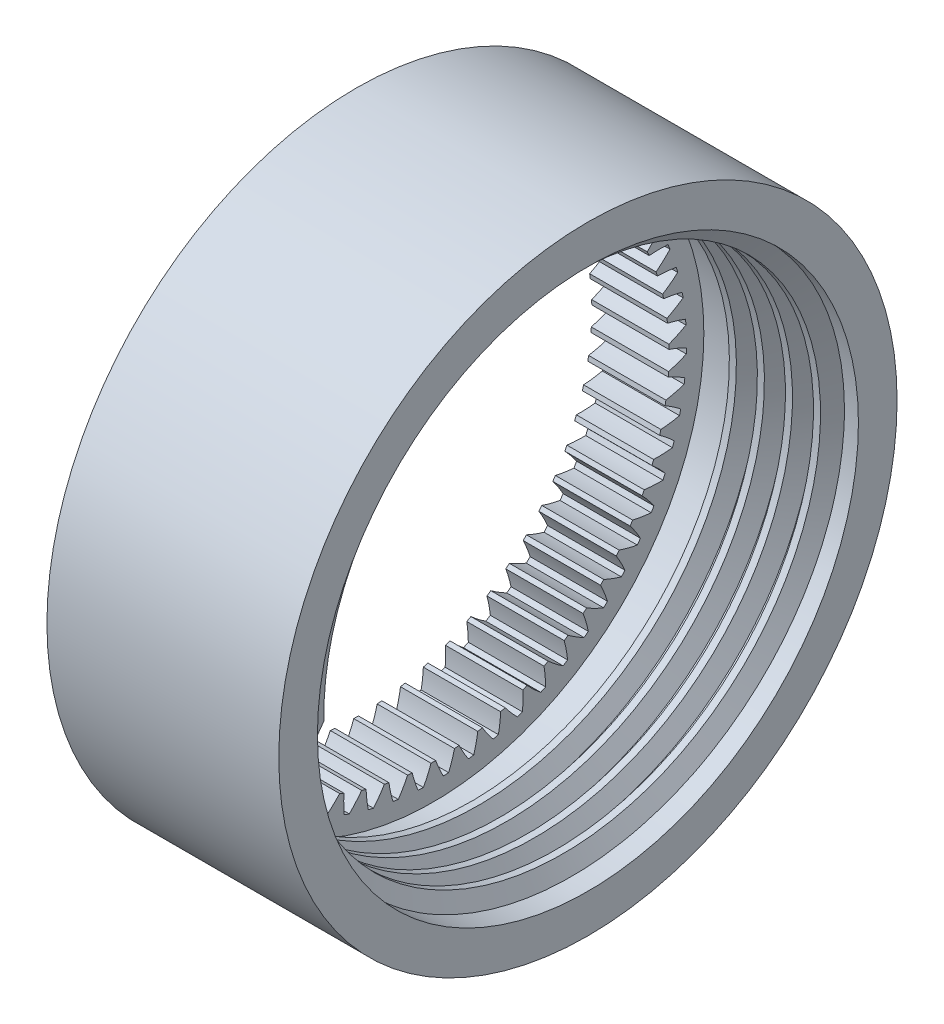
SolidWorks part; units mm, degrees
ref_plane "Front Plane" through (0, 0, 0) normal (0, 0, 1) x (1, 0, 0)
ref_plane "Top Plane" through (0, 0, 0) normal (0, 1, 0) x (1, 0, 0)
ref_plane "Right Plane" through (0, 0, 0) normal (1, 0, 0) x (0, 0, -1)
ref_plane "Plane1" through (-10.9631, 0, 0) normal (1, 0, 0) x (0, 0, -1)
sketch "Sketch1" plane through (-10.9631, 0, 0) normal (1, 0, 0) x (0, 0, -1)
  circle A0 centre (-14.8751, -9.4962) radius 40
  arc A1 (-13.054, 20.9494) -> (-11.9585, 23.1247) centre (1.5185, 14.9741) cw
  arc A2 (-11.9585, 23.1247) -> (-11.2701, 23.0558) centre (-14.8751, -9.4962) cw
  arc A3 (-11.2701, 23.0558) -> (-10.6273, 20.7066) centre (-26.0949, 17.7372) cw
  arc A4 (-10.6273, 20.7066) -> (-10.0317, 20.6168) centre (-14.8751, -9.4962) cw
  arc A5 (-10.0317, 20.6168) -> (-8.725, 22.6722) centre (3.8735, 13.2202) cw
  arc A6 (-8.725, 22.6722) -> (-8.0468, 22.5351) centre (-14.8751, -9.4962) cw
  arc A7 (-8.0468, 22.5351) -> (-7.6412, 20.1336) centre (-23.3275, 18.7191) cw
  arc A8 (-7.6412, 20.1336) -> (-7.0574, 19.9849) centre (-14.8751, -9.4962) cw
  arc A9 (-7.0574, 19.9849) -> (-5.5526, 21.9) centre (6.0421, 11.2406) cw
  arc A10 (-5.5526, 21.9) -> (-4.8915, 21.6961) centre (-14.8751, -9.4962) cw
  arc A11 (-4.8915, 21.6961) -> (-4.727, 19.2661) centre (-20.4762, 19.4204) cw
  arc A12 (-4.727, 19.2661) -> (-4.1609, 19.0601) centre (-14.8751, -9.4962) cw
  arc A13 (-4.1609, 19.0601) -> (-2.4729, 20.8158) centre (8.0029, 9.0549) cw
  arc A14 (-2.4729, 20.8158) -> (-1.8353, 20.5471) centre (-14.8751, -9.4962) cw
  arc A15 (-1.8353, 20.5471) -> (-1.9136, 18.1127) centre (-17.5692, 19.8344) cw
  arc A16 (-1.9136, 18.1127) -> (-1.3709, 17.8514) centre (-14.8751, -9.4962) cw
  arc A17 (-1.3709, 17.8514) -> (0.4835, 19.4303) centre (9.7363, 6.6848) cw
  arc A18 (0.4835, 19.4303) -> (1.0912, 19.0994) centre (-14.8751, -9.4962) cw
  arc A19 (1.0912, 19.0994) -> (0.7709, 16.685) centre (-14.6354, 19.9569) cw
  arc A20 (0.7709, 16.685) -> (1.2849, 16.3709) centre (-14.8751, -9.4962) cw
  arc A21 (1.2849, 16.3709) -> (3.2874, 17.7574) centre (11.2251, 4.1539) cw
  arc A22 (3.2874, 17.7574) -> (3.8591, 17.3676) centre (-14.8751, -9.4962) cw
  arc A23 (3.8591, 17.3676) -> (3.3, 14.9971) centre (-11.7041, 19.7867) cw
  arc A24 (3.3, 14.9971) -> (3.7802, 14.6333) centre (-14.8751, -9.4962) cw
  arc A25 (3.7802, 14.6333) -> (5.9107, 15.8135) centre (12.4545, 1.4873) cw
  arc A26 (5.9107, 15.8135) -> (6.4407, 15.3688) centre (-14.8751, -9.4962) cw
  arc A27 (6.4407, 15.3688) -> (5.6484, 13.0657) centre (-8.8042, 19.3255) cw
  arc A28 (5.6484, 13.0657) -> (6.09, 12.656) centre (-14.8751, -9.4962) cw
  arc A29 (6.09, 12.656) -> (8.3274, 13.6182) centre (13.4123, -1.2884) cw
  arc A30 (8.3274, 13.6182) -> (8.8105, 13.1229) centre (-14.8751, -9.4962) cw
  arc A31 (8.8105, 13.1229) -> (7.7929, 10.9101) centre (-5.9646, 18.5778) cw
  arc A32 (7.7929, 10.9101) -> (8.1915, 10.4585) centre (-14.8751, -9.4962) cw
  arc A33 (8.1915, 10.4585) -> (10.5136, 11.1931) centre (14.089, -4.1457) cw
  arc A34 (10.5136, 11.1931) -> (10.945, 10.6521) centre (-14.8751, -9.4962) cw
  arc A35 (10.945, 10.6521) -> (9.712, 8.5517) centre (-3.2137, 17.5511) cw
  arc A36 (9.712, 8.5517) -> (10.0637, 8.0626) centre (-14.8751, -9.4962) cw
  arc A37 (10.0637, 8.0626) -> (12.4474, 8.5624) centre (14.4778, -7.0562) cw
  arc A38 (12.4474, 8.5624) -> (12.8228, 7.9812) centre (-14.8751, -9.4962) cw
  arc A39 (12.8228, 7.9812) -> (11.3868, 6.0139) centre (-0.5786, 16.2556) cw
  arc A40 (11.3868, 6.0139) -> (11.688, 5.4923) centre (-14.8751, -9.4962) cw
  arc A41 (11.688, 5.4923) -> (14.1097, 5.7522) centre (14.5749, -9.9909) cw
  arc A42 (14.1097, 5.7522) -> (14.4253, 5.1365) centre (-14.8751, -9.4962) cw
  arc A43 (14.4253, 5.1365) -> (12.8006, 3.322) centre (1.9144, 14.7042) cw
  arc A44 (12.8006, 3.322) -> (13.0484, 2.773) centre (-14.8751, -9.4962) cw
  arc A45 (13.0484, 2.773) -> (15.4839, 2.7905) centre (14.3793, -12.9207) cw
  arc A46 (15.4839, 2.7905) -> (15.7367, 2.1464) centre (-14.8751, -9.4962) cw
  arc A47 (15.7367, 2.1464) -> (13.9394, 0.5027) centre (4.2406, 12.9122) cw
  arc A48 (13.9394, 0.5027) -> (14.1312, -0.0683) centre (-14.8751, -9.4962) cw
  arc A49 (14.1312, -0.0683) -> (16.5564, -0.2933) centre (13.8929, -15.8165) cw
  arc A50 (16.5564, -0.2933) -> (16.7438, -0.9594) centre (-14.8751, -9.4962) cw
  arc A51 (16.7438, -0.9594) -> (14.7918, -2.416) centre (6.3767, 10.8976) cw
  arc A52 (14.7918, -2.416) -> (14.9258, -3.0032) centre (-14.8751, -9.4962) cw
  arc A53 (14.9258, -3.0032) -> (17.3165, -3.4686) centre (13.1207, -18.6494) cw
  arc A54 (17.3165, -3.4686) -> (17.4367, -4.15) centre (-14.8751, -9.4962) cw
  arc A55 (17.4367, -4.15) -> (15.3493, -5.405) centre (8.3017, 8.6802) cw
  arc A56 (15.3493, -5.405) -> (15.4242, -6.0027) centre (-14.8751, -9.4962) cw
  arc A57 (15.4242, -6.0027) -> (17.7567, -6.7038) centre (12.0702, -21.3914) cw
  arc A58 (17.7567, -6.7038) -> (17.8084, -7.3938) centre (-14.8751, -9.4962) cw
  arc A59 (17.8084, -7.3938) -> (15.6065, -8.4347) centre (9.9963, 6.2822) cw
  arc A60 (15.6065, -8.4347) -> (15.6215, -9.0369) centre (-14.8751, -9.4962) cw
  arc A61 (15.6215, -9.0369) -> (17.8726, -9.9668) centre (10.7519, -24.0152) cw
  arc A62 (17.8726, -9.9668) -> (17.8553, -10.6585) centre (-14.8751, -9.4962) cw
  arc A63 (17.8553, -10.6585) -> (15.5607, -11.475) centre (11.4437, 3.7274) cw
  arc A64 (15.5607, -11.475) -> (15.5157, -12.0757) centre (-14.8751, -9.4962) cw
  arc A65 (15.5157, -12.0757) -> (17.663, -13.225) centre (9.1789, -26.4947) cw
  arc A66 (17.663, -13.225) -> (17.5769, -13.9116) centre (-14.8751, -9.4962) cw
  arc A67 (17.5769, -13.9116) -> (15.2124, -14.4955) centre (12.6296, 1.0412) cw
  arc A68 (15.2124, -14.4955) -> (15.1078, -15.0888) centre (-14.8751, -9.4962) cw
  arc A69 (15.1078, -15.0888) -> (17.13, -16.4463) centre (7.3669, -28.8052) cw
  arc A70 (17.13, -16.4463) -> (16.976, -17.1208) centre (-14.8751, -9.4962) cw
  arc A71 (16.976, -17.1208) -> (14.5651, -17.4665) centre (13.5421, -1.7497) cw
  arc A72 (14.5651, -17.4665) -> (14.402, -18.0463) centre (-14.8751, -9.4962) cw
  arc A73 (14.402, -18.0463) -> (16.279, -19.5984) centre (5.3338, -30.9238) cw
  arc A74 (16.279, -19.5984) -> (16.0586, -20.2543) centre (-14.8751, -9.4962) cw
  arc A75 (16.0586, -20.2543) -> (13.6252, -20.3581) centre (14.1722, -4.6176) cw
  arc A76 (13.6252, -20.3581) -> (13.4052, -20.9189) centre (-14.8751, -9.4962) cw
  arc A77 (13.4052, -20.9189) -> (15.1183, -22.6501) centre (3.0999, -32.8295) cw
  arc A78 (15.1183, -22.6501) -> (14.8337, -23.2808) centre (-14.8751, -9.4962) cw
  arc A79 (14.8337, -23.2808) -> (12.4021, -23.1419) centre (14.5136, -7.5341) cw
  arc A80 (12.4021, -23.1419) -> (12.1273, -23.6779) centre (-14.8751, -9.4962) cw
  arc A81 (12.1273, -23.6779) -> (13.6595, -25.5711) centre (0.6873, -34.5033) cw
  arc A82 (13.6595, -25.5711) -> (13.3136, -26.1703) centre (-14.8751, -9.4962) cw
  arc A83 (13.3136, -26.1703) -> (10.9079, -25.79) centre (14.5629, -10.47) cw
  arc A84 (10.9079, -25.79) -> (10.5811, -26.296) centre (-14.8751, -9.4962) cw
  arc A85 (10.5811, -26.296) -> (11.9172, -28.3324) centre (-1.88, -35.9285) cw
  arc A86 (11.9172, -28.3324) -> (11.5133, -28.8942) centre (-14.8751, -9.4962) cw
  arc A87 (11.5133, -28.8942) -> (9.1574, -28.2762) centre (14.3197, -13.3962) cw
  arc A88 (9.1574, -28.2762) -> (8.7819, -28.7471) centre (-14.8751, -9.4962) cw
  arc A89 (8.7819, -28.7471) -> (9.9086, -30.9064) centre (-4.5763, -37.0911) cw
  arc A90 (9.9086, -30.9064) -> (9.4508, -31.4252) centre (-14.8751, -9.4962) cw
  arc A91 (9.4508, -31.4252) -> (7.1681, -30.5757) centre (13.7863, -16.2837) cw
  arc A92 (7.1681, -30.5757) -> (6.7475, -31.0069) centre (-14.8751, -9.4962) cw
  arc A93 (6.7475, -31.0069) -> (7.6536, -33.2677) centre (-7.3751, -37.9794) cw
  arc A94 (7.6536, -33.2677) -> (7.1464, -33.7383) centre (-14.8751, -9.4962) cw
  arc A95 (7.1464, -33.7383) -> (4.9597, -32.6658) centre (12.968, -19.1037) cw
  arc A96 (4.9597, -32.6658) -> (4.4983, -33.053) centre (-14.8751, -9.4962) cw
  arc A97 (4.4983, -33.053) -> (5.1748, -35.3927) centre (-10.2484, -38.5846) cw
  arc A98 (5.1748, -35.3927) -> (4.6233, -35.8105) centre (-14.8751, -9.4962) cw
  arc A99 (4.6233, -35.8105) -> (2.5542, -34.5255) centre (11.8731, -21.8282) cw
  arc A100 (2.5542, -34.5255) -> (2.0565, -34.8649) centre (-14.8751, -9.4962) cw
  arc A101 (2.0565, -34.8649) -> (2.4967, -37.2603) centre (-13.1676, -38.9007) cw
  arc A102 (2.4967, -37.2603) -> (1.9063, -37.6211) centre (-14.8751, -9.4962) cw
  arc A103 (1.9063, -37.6211) -> (-0.0245, -36.1366) centre (10.5123, -24.4302) cw
  arc A104 (-0.0245, -36.1366) -> (-0.5535, -36.4246) centre (-14.8751, -9.4962) cw
  arc A105 (-0.5535, -36.4246) -> (-0.354, -38.852) centre (-16.1039, -38.9246) cw
  arc A106 (-0.354, -38.852) -> (-0.9774, -39.1522) centre (-14.8751, -9.4962) cw
  arc A107 (-0.9774, -39.1522) -> (-2.7508, -37.4828) centre (8.8992, -26.8838) cw
  arc A108 (-2.7508, -37.4828) -> (-3.3059, -37.7168) centre (-14.8751, -9.4962) cw
  arc A109 (-3.3059, -37.7168) -> (-3.3491, -40.152) centre (-19.0279, -38.656) cw
  arc A110 (-3.3491, -40.152) -> (-3.9993, -40.3886) centre (-14.8751, -9.4962) cw
  arc A111 (-3.9993, -40.3886) -> (-5.5977, -38.5509) centre (7.0498, -29.1645) cw
  arc A112 (-5.5977, -38.5509) -> (-6.1733, -38.7285) centre (-14.8751, -9.4962) cw
  arc A113 (-6.1733, -38.7285) -> (-6.4587, -41.1473) centre (-21.9106, -38.0976) cw
  arc A114 (-6.4587, -41.1473) -> (-7.1292, -41.318) centre (-14.8751, -9.4962) cw
  arc A115 (-7.1292, -41.318) -> (-8.5367, -39.3303) centre (4.9825, -31.2498) cw
  arc A116 (-8.5367, -39.3303) -> (-9.1271, -39.4496) centre (-14.8751, -9.4962) cw
  arc A117 (-9.1271, -39.4496) -> (-9.652, -41.828) centre (-24.7235, -37.255) cw
  arc A118 (-9.652, -41.828) -> (-10.3361, -41.9311) centre (-14.8751, -9.4962) cw
  arc A119 (-10.3361, -41.9311) -> (-11.5387, -39.8131) centre (2.7179, -33.1188) cw
  arc A120 (-11.5387, -39.8131) -> (-12.1381, -39.8731) centre (-14.8751, -9.4962) cw
  arc A121 (-12.1381, -39.8731) -> (-12.8971, -42.1874) centre (-27.4384, -36.1364) cw
  arc A122 (-12.8971, -42.1874) -> (-13.5882, -42.2219) centre (-14.8751, -9.4962) cw
  arc A123 (-13.5882, -42.2219) -> (-14.5739, -39.9947) centre (0.2784, -34.7532) cw
  arc A124 (-14.5739, -39.9947) -> (-15.1762, -39.9947) centre (-14.8751, -9.4962) cw
  arc A125 (-15.1762, -39.9947) -> (-16.1619, -42.2219) centre (-30.0285, -34.7532) cw
  arc A126 (-16.1619, -42.2219) -> (-16.853, -42.1874) centre (-14.8751, -9.4962) cw
  arc A127 (-16.853, -42.1874) -> (-17.612, -39.8731) centre (-2.3117, -36.1364) cw
  arc A128 (-17.612, -39.8731) -> (-18.2114, -39.8131) centre (-14.8751, -9.4962) cw
  arc A129 (-18.2114, -39.8131) -> (-19.414, -41.9311) centre (-32.468, -33.1188) cw
  arc A130 (-19.414, -41.9311) -> (-20.0982, -41.828) centre (-14.8751, -9.4962) cw
  arc A131 (-20.0982, -41.828) -> (-20.623, -39.4496) centre (-5.0267, -37.255) cw
  arc A132 (-20.623, -39.4496) -> (-21.2134, -39.3303) centre (-14.8751, -9.4962) cw
  arc A133 (-21.2134, -39.3303) -> (-22.6209, -41.318) centre (-34.7326, -31.2498) cw
  arc A134 (-22.6209, -41.318) -> (-23.2914, -41.1473) centre (-14.8751, -9.4962) cw
  arc A135 (-23.2914, -41.1473) -> (-23.5768, -38.7285) centre (-7.8395, -38.0976) cw
  arc A136 (-23.5768, -38.7285) -> (-24.1525, -38.5509) centre (-14.8751, -9.4962) cw
  arc A137 (-24.1525, -38.5509) -> (-25.7508, -40.3886) centre (-36.7999, -29.1645) cw
  arc A138 (-25.7508, -40.3886) -> (-26.401, -40.152) centre (-14.8751, -9.4962) cw
  arc A139 (-26.401, -40.152) -> (-26.4442, -37.7168) centre (-10.7222, -38.656) cw
  arc A140 (-26.4442, -37.7168) -> (-26.9993, -37.4828) centre (-14.8751, -9.4962) cw
  arc A141 (-26.9993, -37.4828) -> (-28.7727, -39.1522) centre (-38.6493, -26.8838) cw
  arc A142 (-28.7727, -39.1522) -> (-29.3961, -38.852) centre (-14.8751, -9.4962) cw
  arc A143 (-29.3961, -38.852) -> (-29.1966, -36.4246) centre (-13.6462, -38.9246) cw
  arc A144 (-29.1966, -36.4246) -> (-29.7256, -36.1366) centre (-14.8751, -9.4962) cw
  arc A145 (-29.7256, -36.1366) -> (-31.6564, -37.6211) centre (-40.2624, -24.4302) cw
  arc A146 (-31.6564, -37.6211) -> (-32.2468, -37.2603) centre (-14.8751, -9.4962) cw
  arc A147 (-32.2468, -37.2603) -> (-31.8066, -34.8649) centre (-16.5825, -38.9007) cw
  arc A148 (-31.8066, -34.8649) -> (-32.3043, -34.5255) centre (-14.8751, -9.4962) cw
  arc A149 (-32.3043, -34.5255) -> (-34.3734, -35.8105) centre (-41.6232, -21.8282) cw
  arc A150 (-34.3734, -35.8105) -> (-34.9249, -35.3927) centre (-14.8751, -9.4962) cw
  arc A151 (-34.9249, -35.3927) -> (-34.2484, -33.053) centre (-19.5017, -38.5846) cw
  arc A152 (-34.2484, -33.053) -> (-34.7098, -32.6658) centre (-14.8751, -9.4962) cw
  arc A153 (-34.7098, -32.6658) -> (-36.8965, -33.7383) centre (-42.7181, -19.1037) cw
  arc A154 (-36.8965, -33.7383) -> (-37.4037, -33.2677) centre (-14.8751, -9.4962) cw
  arc A155 (-37.4037, -33.2677) -> (-36.4976, -31.0069) centre (-22.375, -37.9794) cw
  arc A156 (-36.4976, -31.0069) -> (-36.9182, -30.5757) centre (-14.8751, -9.4962) cw
  arc A157 (-36.9182, -30.5757) -> (-39.2009, -31.4252) centre (-43.5364, -16.2837) cw
  arc A158 (-39.2009, -31.4252) -> (-39.6587, -30.9064) centre (-14.8751, -9.4962) cw
  arc A159 (-39.6587, -30.9064) -> (-38.532, -28.7471) centre (-25.1738, -37.0911) cw
  arc A160 (-38.532, -28.7471) -> (-38.9075, -28.2762) centre (-14.8751, -9.4962) cw
  arc A161 (-38.9075, -28.2762) -> (-41.2634, -28.8942) centre (-44.0698, -13.3962) cw
  arc A162 (-41.2634, -28.8942) -> (-41.6673, -28.3324) centre (-14.8751, -9.4962) cw
  arc A163 (-41.6673, -28.3324) -> (-40.3312, -26.296) centre (-27.8702, -35.9285) cw
  arc A164 (-40.3312, -26.296) -> (-40.658, -25.79) centre (-14.8751, -9.4962) cw
  arc A165 (-40.658, -25.79) -> (-43.0637, -26.1703) centre (-44.313, -10.47) cw
  arc A166 (-43.0637, -26.1703) -> (-43.4096, -25.5711) centre (-14.8751, -9.4962) cw
  arc A167 (-43.4096, -25.5711) -> (-41.8774, -23.6779) centre (-30.4374, -34.5033) cw
  arc A168 (-41.8774, -23.6779) -> (-42.1522, -23.1419) centre (-14.8751, -9.4962) cw
  arc A169 (-42.1522, -23.1419) -> (-44.5838, -23.2808) centre (-44.2637, -7.5341) cw
  arc A170 (-44.5838, -23.2808) -> (-44.8684, -22.6501) centre (-14.8751, -9.4962) cw
  arc A171 (-44.8684, -22.6501) -> (-43.1553, -20.9189) centre (-32.85, -32.8295) cw
  arc A172 (-43.1553, -20.9189) -> (-43.3754, -20.3581) centre (-14.8751, -9.4962) cw
  arc A173 (-43.3754, -20.3581) -> (-45.8087, -20.2543) centre (-43.9223, -4.6176) cw
  arc A174 (-45.8087, -20.2543) -> (-46.0291, -19.5984) centre (-14.8751, -9.4962) cw
  arc A175 (-46.0291, -19.5984) -> (-44.1521, -18.0463) centre (-35.0839, -30.9238) cw
  arc A176 (-44.1521, -18.0463) -> (-44.3152, -17.4665) centre (-14.8751, -9.4962) cw
  arc A177 (-44.3152, -17.4665) -> (-46.7262, -17.1208) centre (-43.2922, -1.7497) cw
  arc A178 (-46.7262, -17.1208) -> (-46.8801, -16.4463) centre (-14.8751, -9.4962) cw
  arc A179 (-46.8801, -16.4463) -> (-44.8579, -15.0888) centre (-37.117, -28.8052) cw
  arc A180 (-44.8579, -15.0888) -> (-44.9625, -14.4955) centre (-14.8751, -9.4962) cw
  arc A181 (-44.9625, -14.4955) -> (-47.327, -13.9116) centre (-42.3797, 1.0412) cw
  arc A182 (-47.327, -13.9116) -> (-47.4131, -13.225) centre (-14.8751, -9.4962) cw
  arc A183 (-47.4131, -13.225) -> (-45.2658, -12.0757) centre (-38.929, -26.4947) cw
  arc A184 (-45.2658, -12.0757) -> (-45.3108, -11.475) centre (-14.8751, -9.4962) cw
  arc A185 (-45.3108, -11.475) -> (-47.6054, -10.6585) centre (-41.1938, 3.7274) cw
  arc A186 (-47.6054, -10.6585) -> (-47.6227, -9.9668) centre (-14.8751, -9.4962) cw
  arc A187 (-47.6227, -9.9668) -> (-45.3716, -9.0369) centre (-40.502, -24.0152) cw
  arc A188 (-45.3716, -9.0369) -> (-45.3566, -8.4347) centre (-14.8751, -9.4962) cw
  arc A189 (-45.3566, -8.4347) -> (-47.5585, -7.3938) centre (-39.7464, 6.2822) cw
  arc A190 (-47.5585, -7.3938) -> (-47.5068, -6.7038) centre (-14.8751, -9.4962) cw
  arc A191 (-47.5068, -6.7038) -> (-45.1743, -6.0027) centre (-41.8203, -21.3914) cw
  arc A192 (-45.1743, -6.0027) -> (-45.0994, -5.405) centre (-14.8751, -9.4962) cw
  arc A193 (-45.0994, -5.405) -> (-47.1868, -4.15) centre (-38.0518, 8.6802) cw
  arc A194 (-47.1868, -4.15) -> (-47.0666, -3.4686) centre (-14.8751, -9.4962) cw
  arc A195 (-47.0666, -3.4686) -> (-44.6759, -3.0032) centre (-42.8708, -18.6494) cw
  arc A196 (-44.6759, -3.0032) -> (-44.5419, -2.416) centre (-14.8751, -9.4962) cw
  arc A197 (-44.5419, -2.416) -> (-46.4939, -0.9594) centre (-36.1269, 10.8976) cw
  arc A198 (-46.4939, -0.9594) -> (-46.3065, -0.2933) centre (-14.8751, -9.4962) cw
  arc A199 (-46.3065, -0.2933) -> (-43.8814, -0.0683) centre (-43.643, -15.8165) cw
  arc A200 (-43.8814, -0.0683) -> (-43.6895, 0.5027) centre (-14.8751, -9.4962) cw
  arc A201 (-43.6895, 0.5027) -> (-45.4868, 2.1464) centre (-33.9907, 12.9122) cw
  arc A202 (-45.4868, 2.1464) -> (-45.234, 2.7905) centre (-14.8751, -9.4962) cw
  arc A203 (-45.234, 2.7905) -> (-42.7985, 2.773) centre (-44.1294, -12.9207) cw
  arc A204 (-42.7985, 2.773) -> (-42.5508, 3.322) centre (-14.8751, -9.4962) cw
  arc A205 (-42.5508, 3.322) -> (-44.1754, 5.1365) centre (-31.6645, 14.7042) cw
  arc A206 (-44.1754, 5.1365) -> (-43.8598, 5.7522) centre (-14.8751, -9.4962) cw
  arc A207 (-43.8598, 5.7522) -> (-41.4381, 5.4923) centre (-44.325, -9.9909) cw
  arc A208 (-41.4381, 5.4923) -> (-41.1369, 6.0139) centre (-14.8751, -9.4962) cw
  arc A209 (-41.1369, 6.0139) -> (-42.5729, 7.9812) centre (-29.1715, 16.2556) cw
  arc A210 (-42.5729, 7.9812) -> (-42.1975, 8.5624) centre (-14.8751, -9.4962) cw
  arc A211 (-42.1975, 8.5624) -> (-39.8138, 8.0626) centre (-44.2279, -7.0562) cw
  arc A212 (-39.8138, 8.0626) -> (-39.4621, 8.5517) centre (-14.8751, -9.4962) cw
  arc A213 (-39.4621, 8.5517) -> (-40.6951, 10.6521) centre (-26.5365, 17.5511) cw
  arc A214 (-40.6951, 10.6521) -> (-40.2637, 11.1931) centre (-14.8751, -9.4962) cw
  arc A215 (-40.2637, 11.1931) -> (-37.9416, 10.4585) centre (-43.8391, -4.1457) cw
  arc A216 (-37.9416, 10.4585) -> (-37.543, 10.9101) centre (-14.8751, -9.4962) cw
  arc A217 (-37.543, 10.9101) -> (-38.5607, 13.1229) centre (-23.7855, 18.5778) cw
  arc A218 (-38.5607, 13.1229) -> (-38.0775, 13.6182) centre (-14.8751, -9.4962) cw
  arc A219 (-38.0775, 13.6182) -> (-35.8401, 12.656) centre (-43.1624, -1.2884) cw
  arc A220 (-35.8401, 12.656) -> (-35.3985, 13.0657) centre (-14.8751, -9.4962) cw
  arc A221 (-35.3985, 13.0657) -> (-36.1908, 15.3688) centre (-20.9459, 19.3255) cw
  arc A222 (-36.1908, 15.3688) -> (-35.6608, 15.8135) centre (-14.8751, -9.4962) cw
  arc A223 (-35.6608, 15.8135) -> (-33.5303, 14.6333) centre (-42.2046, 1.4873) cw
  arc A224 (-33.5303, 14.6333) -> (-33.0501, 14.9971) centre (-14.8751, -9.4962) cw
  arc A225 (-33.0501, 14.9971) -> (-33.6092, 17.3676) centre (-18.046, 19.7867) cw
  arc A226 (-33.6092, 17.3676) -> (-33.0375, 17.7574) centre (-14.8751, -9.4962) cw
  arc A227 (-33.0375, 17.7574) -> (-31.0351, 16.3709) centre (-40.9752, 4.1539) cw
  arc A228 (-31.0351, 16.3709) -> (-30.521, 16.685) centre (-14.8751, -9.4962) cw
  arc A229 (-30.521, 16.685) -> (-30.8413, 19.0994) centre (-15.1147, 19.9569) cw
  arc A230 (-30.8413, 19.0994) -> (-30.2337, 19.4303) centre (-14.8751, -9.4962) cw
  arc A231 (-30.2337, 19.4303) -> (-28.3792, 17.8514) centre (-39.4864, 6.6848) cw
  arc A232 (-28.3792, 17.8514) -> (-27.8365, 18.1127) centre (-14.8751, -9.4962) cw
  arc A233 (-27.8365, 18.1127) -> (-27.9148, 20.5471) centre (-12.1809, 19.8344) cw
  arc A234 (-27.9148, 20.5471) -> (-27.2772, 20.8158) centre (-14.8751, -9.4962) cw
  arc A235 (-27.2772, 20.8158) -> (-25.5892, 19.0601) centre (-37.753, 9.0549) cw
  arc A236 (-25.5892, 19.0601) -> (-25.0231, 19.2661) centre (-14.8751, -9.4962) cw
  arc A237 (-25.0231, 19.2661) -> (-24.8586, 21.6961) centre (-9.2739, 19.4204) cw
  arc A238 (-24.8586, 21.6961) -> (-24.1975, 21.9) centre (-14.8751, -9.4962) cw
  arc A239 (-24.1975, 21.9) -> (-22.6927, 19.9849) centre (-35.7922, 11.2406) cw
  arc A240 (-22.6927, 19.9849) -> (-22.1089, 20.1336) centre (-14.8751, -9.4962) cw
  arc A241 (-22.1089, 20.1336) -> (-21.7033, 22.5351) centre (-6.4226, 18.7191) cw
  arc A242 (-21.7033, 22.5351) -> (-21.0251, 22.6722) centre (-14.8751, -9.4962) cw
  arc A243 (-21.0251, 22.6722) -> (-19.7184, 20.6168) centre (-33.6236, 13.2202) cw
  arc A244 (-19.7184, 20.6168) -> (-19.1228, 20.7066) centre (-14.8751, -9.4962) cw
  arc A245 (-19.1228, 20.7066) -> (-18.48, 23.0558) centre (-3.6552, 17.7372) cw
  arc A246 (-18.48, 23.0558) -> (-17.7916, 23.1247) centre (-14.8751, -9.4962) cw
  arc A247 (-17.7916, 23.1247) -> (-16.6961, 20.9494) centre (-31.2686, 14.9741) cw
  arc A248 (-16.6961, 20.9494) -> (-16.0945, 20.9795) centre (-14.8751, -9.4962) cw
  arc A249 (-16.0945, 20.9795) -> (-15.221, 23.253) centre (-0.9994, 16.4848) cw
  arc A250 (-15.221, 23.253) -> (-14.5291, 23.253) centre (-14.8751, -9.4962) cw
  arc A251 (-14.5291, 23.253) -> (-13.6556, 20.9795) centre (-28.7507, 16.4848) cw
  arc A252 (-13.6556, 20.9795) -> (-13.054, 20.9494) centre (-14.8751, -9.4962) cw
extrude "Boss-Extrude1" add sketch "Sketch1" against normal blind 10
sketch "Sketch2" plane through (-10.9631, 0, 0) normal (1, 0, 0) x (0, 0, -1)
  circle A0 centre (-14.8751, -9.4962) radius 40
  circle A1 centre (-14.8751, -9.4962) radius 40 construction
  circle A2 centre (-14.8751, -9.4962) radius 35
  dimension "D1" = 5
  dimension "D2" = 70
extrude "Boss-Extrude2" add sketch "Sketch2" along normal blind 20
thread "Thread1" pitch 3.6286 method extrude profile "Thread Profile1" start angle 0, offset 0, length 15, pitch 3.6286, diameter 70
ref_plane "Plane2" through (9.0369, -9.4962, 49.8751) normal (0, -1, 0) x (0, 0, 1)
sketch "Thread Profile1" plane through (9.0369, -9.4962, 49.8751) normal (0, -1, 0) x (0, 0, 1)
  line L0 (0, 0) -> (0, 3.6286) construction
  line L11 (0, 0) -> (0, 3.175)
  line L12 (0, 3.175) -> (-1.964, 2.0411)
  line L13 (-1.964, 2.0411) -> (-1.964, 1.1339)
  line L15 (-1.964, 1.1339) -> (0, 0)
  line L17 (-1.964, 1.5875) -> (0, 1.5875) construction
  point P2 (0, 0)
  dimension "Pitch" = 3.6286
  dimension "Profile_Angle" = 60
  dimension "Profile_Land" = 0.9071
  dimension "Profile_Height" = 1.964
